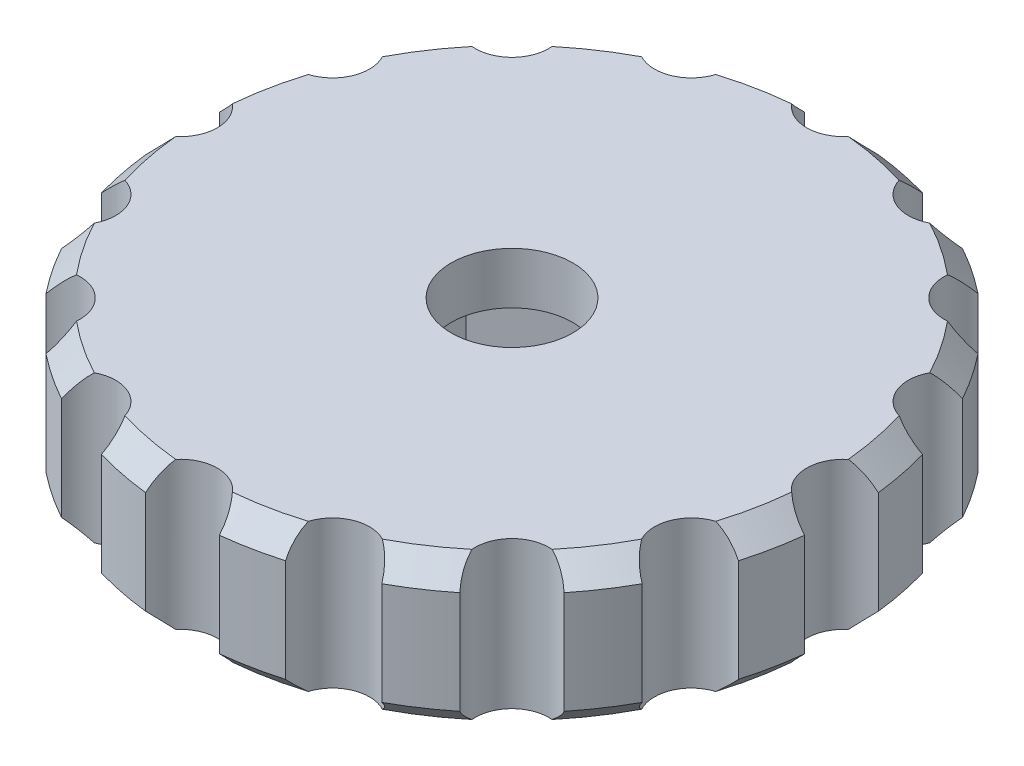
SolidWorks part; units mm, degrees
ref_plane "Front Plane" through (0, 0, 0) normal (0, 0, 1) x (1, 0, 0)
ref_plane "Top Plane" through (0, 0, 0) normal (0, 1, 0) x (1, 0, 0)
ref_plane "Right Plane" through (0, 0, 0) normal (1, 0, 0) x (0, 0, -1)
sketch "Sketch1" plane through (0, 0, 0) normal (0, 1, 0) x (1, 0, 0)
  circle A0 centre (0, 0) radius 9
  dimension "D1" = 18
extrude "Boss-Extrude1" add sketch "Sketch1" along normal blind 4
sketch "Sketch2" plane through (0, 0, 0) normal (0, -1, 0) x (1, 0, 0)
  line L1 (2.95, 1.7032) -> (0, 3.4064)
  line L2 (0, 3.4064) -> (-2.95, 1.7032)
  line L3 (-2.95, 1.7032) -> (-2.95, -1.7032)
  line L4 (-2.95, -1.7032) -> (0, -3.4064)
  line L5 (0, -3.4064) -> (2.95, -1.7032)
  line L6 (2.95, -1.7032) -> (2.95, 1.7032)
  circle A0 centre (0, 0) radius 2.95 construction
  point P1 (0, 0)
  dimension "D1" = 5.9
extrude "Cut-Extrude1" cut sketch "Sketch2" against normal blind 2.6
sketch "Sketch3" plane through (0, 0, 0) normal (0, -1, 0) x (1, 0, 0)
  circle A0 centre (0, 0) radius 1.65
  dimension "D1" = 3.3
extrude "Cut-Extrude2" cut sketch "Sketch3" against normal through all
sketch "Sketch4" plane through (0, 4, 0) normal (0, 1, 0) x (1, 0, 0)
  arc A0 (-1, 8.9443) -> (1, 8.9443) centre (0, 9) ccw
  circle A1 centre (0, 0) radius 9 construction
  arc A2 (2.4989, 8.6461) -> (4.3467, 7.8807) centre (3.4442, 8.3149) ccw
  arc A3 (5.6174, 7.0317) -> (7.0317, 5.6174) centre (6.364, 6.364) ccw
  arc A4 (7.8807, 4.3467) -> (8.6461, 2.4989) centre (8.3149, 3.4442) ccw
  arc A5 (8.9443, 1) -> (8.9443, -1) centre (9, 0) ccw
  arc A6 (8.6461, -2.4989) -> (7.8807, -4.3467) centre (8.3149, -3.4442) ccw
  arc A7 (7.0317, -5.6174) -> (5.6174, -7.0317) centre (6.364, -6.364) ccw
  arc A8 (4.3467, -7.8807) -> (2.4989, -8.6461) centre (3.4442, -8.3149) ccw
  arc A9 (1, -8.9443) -> (-1, -8.9443) centre (0, -9) ccw
  arc A10 (-2.4989, -8.6461) -> (-4.3467, -7.8807) centre (-3.4442, -8.3149) ccw
  arc A11 (-5.6174, -7.0317) -> (-7.0317, -5.6174) centre (-6.364, -6.364) ccw
  arc A12 (-7.8807, -4.3467) -> (-8.6461, -2.4989) centre (-8.3149, -3.4442) ccw
  arc A13 (-8.9443, -1) -> (-8.9443, 1) centre (-9, 0) ccw
  arc A14 (-8.6461, 2.4989) -> (-7.8807, 4.3467) centre (-8.3149, 3.4442) ccw
  arc A15 (-7.0317, 5.6174) -> (-5.6174, 7.0317) centre (-6.364, 6.364) ccw
  arc A16 (-4.3467, 7.8807) -> (-2.4989, 8.6461) centre (-3.4442, 8.3149) ccw
  arc A17 (-2.4989, 8.6461) -> (-4.3467, 7.8807) centre (0, 0) ccw
  arc A18 (-5.6174, 7.0317) -> (-7.0317, 5.6174) centre (0, 0) ccw
  arc A19 (-7.8807, 4.3467) -> (-8.6461, 2.4989) centre (0, 0) ccw
  arc A20 (-8.9443, 1) -> (-8.9443, -1) centre (0, 0) ccw
  arc A21 (-8.6461, -2.4989) -> (-7.8807, -4.3467) centre (0, 0) ccw
  arc A22 (-7.0317, -5.6174) -> (-5.6174, -7.0317) centre (0, 0) ccw
  arc A23 (-4.3467, -7.8807) -> (-2.4989, -8.6461) centre (0, 0) ccw
  arc A24 (-1, -8.9443) -> (1, -8.9443) centre (0, 0) ccw
  arc A25 (2.4989, -8.6461) -> (4.3467, -7.8807) centre (0, 0) ccw
  arc A26 (5.6174, -7.0317) -> (7.0317, -5.6174) centre (0, 0) ccw
  arc A27 (7.8807, -4.3467) -> (8.6461, -2.4989) centre (0, 0) ccw
  arc A28 (8.9443, -1) -> (8.9443, 1) centre (0, 0) ccw
  arc A29 (8.6461, 2.4989) -> (7.8807, 4.3467) centre (0, 0) ccw
  arc A30 (7.0317, 5.6174) -> (5.6174, 7.0317) centre (0, 0) ccw
  arc A31 (4.3467, 7.8807) -> (2.4989, 8.6461) centre (0, 0) ccw
  arc A32 (1, 8.9443) -> (-1, 8.9443) centre (0, 0) ccw
  point P53 (3.0404, 8.4709)
  point P54 (0, 0)
  point P55 (0, 0)
  dimension "D1" = 2
  dimension "D2" = 16
extrude "Cut-Extrude4" cut sketch "Sketch4" against normal through all
sketch "Sketch5" plane through (0, 0, 0) normal (0, 0, 1) x (1, 0, 0)
  line L0 (0, 0) -> (0, 4) construction
  line L1 (8.2943, 4.1) -> (9.0443, 3.35)
  line L2 (9.0443, 3.35) -> (9.0443, 4.1)
  line L3 (9.0443, 4.1) -> (8.2943, 4.1)
  line L4 (1, 4) -> (-1, 4) construction
  line L5 (8.9443, 0) -> (8.9443, 4) construction
  line L6 (0, 2) -> (8.9095, 2) construction
  line L7 (9.0443, -0.1) -> (8.2943, -0.1)
  line L8 (9.0443, 0.65) -> (9.0443, -0.1)
  line L9 (8.2943, -0.1) -> (9.0443, 0.65)
  point P14 (8.9443, 2.8493)
  dimension "D1" = 0.1
  dimension "D2" = 0.1
  dimension "D4" = 0.75
revolve "Cut-Revolve1" cut sketch "Sketch5" angle 360 about L0
